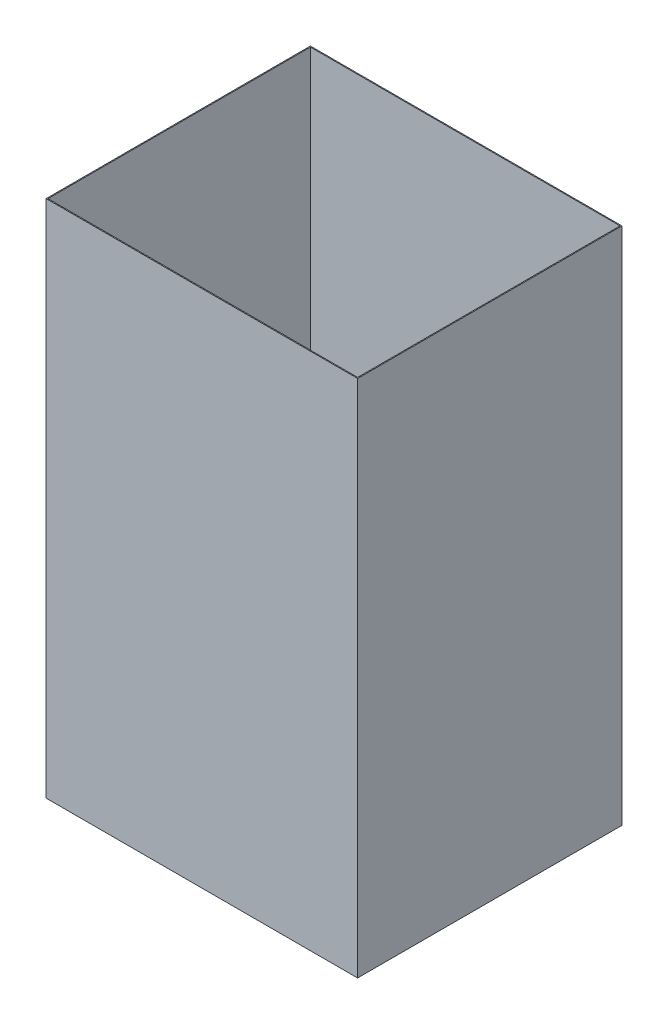
SolidWorks part; units mm, degrees
ref_plane "Front" through (0, 0, 0) normal (0, 0, 1) x (1, 0, 0)
ref_plane "Top" through (0, 0, 0) normal (0, 1, 0) x (1, 0, 0)
ref_plane "Right" through (0, 0, 0) normal (1, 0, 0) x (0, 0, -1)
sketch "Sketch1" plane through (0, 0, 0) normal (0, 1, 0) x (1, 0, 0)
  line L1 (0, 0) -> (838.2, 0)
  line L2 (0, 0) -> (0, 711.2)
  line L3 (0, 711.2) -> (838.2, 711.2)
  line L4 (838.2, 0) -> (838.2, 711.2)
  line L5 (0, 0) -> (838.2, 711.2) construction
  line L6 (0, 711.2) -> (838.2, 0) construction
  point P4 (419.1, 355.6)
  dimension "D1" = 711.2
  dimension "D2" = 838.2
extrude "Boss-Extrude1" add sketch "Sketch1" along normal blind 1397
shell "Shell1" thickness 2.54 removed face at (419.1, 0, -355.6)
ref_plane "Max_Bumper_Height" through (0, 177.8, 0) normal (0, 1, 0) x (1, 0, 0)
sketch "Sketch2" plane through (0, 1394.46, 0) normal (0, -1, 0) x (1, 0, 0)
  line L4 (2.54, -2.54) -> (2.54, -708.66)
  line L5 (2.54, -708.66) -> (835.66, -708.66)
  line L6 (835.66, -708.66) -> (835.66, -2.54)
  line L7 (835.66, -2.54) -> (2.54, -2.54)
  line L8 (2.54, -2.54) -> (2.54, -708.66)
  line L9 (2.54, -708.66) -> (835.66, -708.66)
  line L10 (835.66, -708.66) -> (835.66, -2.54)
  line L11 (835.66, -2.54) -> (2.54, -2.54)
  dimension "D1" = 0
extrude "Cut-Extrude1" cut sketch "Sketch2" against normal up to next
